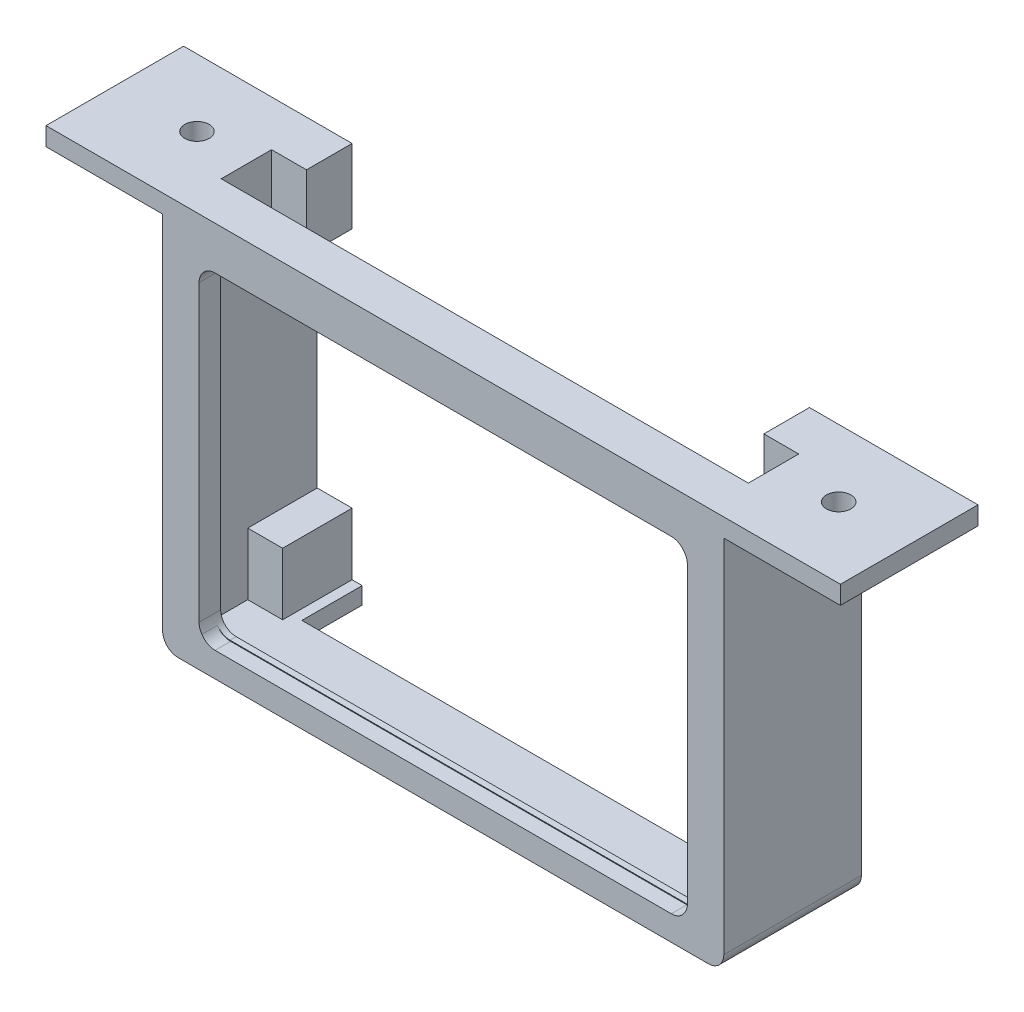
SolidWorks part; units mm, degrees
ref_plane "Front Plane" through (0, 0, 0) normal (0, 0, 1) x (1, 0, 0)
ref_plane "Top Plane" through (0, 0, 0) normal (0, 1, 0) x (1, 0, 0)
ref_plane "Right Plane" through (0, 0, 0) normal (1, 0, 0) x (0, 0, -1)
sketch "Sketch1" plane through (0, 0, 0) normal (0, 0, 1) x (1, 0, 0)
  line L1 (-45.9685, -30.8317) -> (45.9685, -30.8317)
  line L2 (-45.9685, -30.8317) -> (-45.9685, 30.8317)
  line L3 (-45.9685, 30.8317) -> (45.9685, 30.8317)
  line L4 (45.9685, -30.8317) -> (45.9685, 30.8317)
  line L5 (-45.9685, -30.8317) -> (45.9685, 30.8317) construction
  line L6 (-45.9685, 30.8317) -> (45.9685, -30.8317) construction
  line L7 (-43.18, -28.067) -> (43.18, -28.067)
  line L8 (-43.18, -28.067) -> (-43.18, 28.067)
  line L9 (-43.18, 28.067) -> (43.18, 28.067)
  line L10 (43.18, -28.067) -> (43.18, 28.067)
  line L11 (-43.18, -28.067) -> (43.18, 28.067) construction
  line L12 (-43.18, 28.067) -> (43.18, -28.067) construction
  point P0 (0, 0)
  point P6 (0, 0)
extrude "Boss-Extrude1" add sketch "Sketch1" along normal blind 20
sketch "Sketch2" plane through (0, 0, 20) normal (0, 0, 1) x (1, 0, 0)
  line L1 (-43.18, 28.067) -> (43.18, 28.067)
  line L2 (-43.18, 28.067) -> (-43.18, -28.067)
  line L3 (-43.18, -28.067) -> (43.18, -28.067)
  line L4 (43.18, 28.067) -> (43.18, -28.067)
  line L9 (8.8108, -10.2768) -> (-8.8108, 10.2768) construction
  line L10 (8.8108, 10.2768) -> (-8.8108, -10.2768) construction
  line L15 (8.8108, -10.2768) -> (-8.8108, 10.2768) construction
  line L16 (8.8108, 10.2768) -> (-8.8108, -10.2768) construction
  point P6 (0, 0)
  point P12 (0, 0)
extrude "Boss-Extrude3" add sketch "Sketch2" against normal blind 1 contours L2 L1 L4 L3
sketch "Sketch4" plane through (0, 0, 20) normal (0, 0, 1) x (1, 0, 0)
  line L1 (40, -26.64) -> (-40, -26.64)
  line L2 (40, -26.64) -> (40, 26.64)
  line L3 (40, 26.64) -> (-40, 26.64)
  line L4 (-40, -26.64) -> (-40, 26.64)
  line L5 (40, -26.64) -> (-40, 26.64) construction
  line L6 (40, 26.64) -> (-40, -26.64) construction
  point P0 (0, 0)
extrude "Cut-Extrude6" cut sketch "Sketch4" against normal through all
sketch "Sketch5" plane through (0, 30.8317, 0) normal (0, 1, 0) x (1, 0, 0)
  line L0 (45.9685, -20) -> (-45.9685, -20) construction
  line L1 (-77.9537, -20) -> (77.9934, -20)
  line L2 (-77.9537, -20) -> (-77.9537, 0)
  line L3 (-77.9537, 0) -> (77.9934, 0)
  line L4 (77.9934, -20) -> (77.9934, 0)
  line L5 (-77.9537, -20) -> (77.9934, 0) construction
  line L6 (-77.9537, 0) -> (77.9934, -20) construction
  line L7 (45.9685, 0) -> (-45.9685, 0) construction
  point P0 (0.0198, -10)
extrude "Boss-Extrude4" add sketch "Sketch5" along normal blind 3
sketch "Sketch8" plane through (0, 0, 20) normal (0, 0, 1) x (1, 0, 0)
  line L0 (-77.9537, 33.8317) -> (77.9934, 33.8317) construction
  line L1 (45.9685, 30.8317) -> (65.0755, 30.8317)
  line L2 (45.9685, 30.8317) -> (45.9685, 33.8317)
  line L3 (45.9685, 33.8317) -> (65.0755, 33.8317)
  line L4 (65.0755, 30.8317) -> (65.0755, 33.8317)
  line L6 (65.0755, 30.8317) -> (77.9934, 30.8317)
  line L7 (65.0755, 30.8317) -> (65.0755, 33.8317)
  line L8 (65.0755, 33.8317) -> (77.9934, 33.8317)
  line L9 (77.9934, 30.8317) -> (77.9934, 33.8317)
  line M10 (45.9685, 30.8317) -> (77.9934, 30.8317)
  line M11 (77.9934, 30.8317) -> (77.9934, 33.8317)
  line M12 (77.9934, 33.8317) -> (-77.9537, 33.8317)
extrude "Cut-Extrude7" cut sketch "Sketch8" against normal through all contours L4 M10 M11 M12 region at (71.5344, 32.3317, 20)
sketch "Sketch9" plane through (0, 0, 20) normal (0, 0, 1) x (1, 0, 0)
  line L0 (-77.9537, 33.8317) -> (65.0755, 33.8317) construction
  line L1 (-45.9685, 30.8317) -> (-65.0755, 30.8317)
  line L2 (-45.9685, 30.8317) -> (-45.9685, 33.8317)
  line L3 (-45.9685, 33.8317) -> (-65.0755, 33.8317)
  line L4 (-65.0755, 30.8317) -> (-65.0755, 33.8317)
  line L6 (-65.0755, 30.8317) -> (-77.9537, 30.8317)
  line L7 (-65.0755, 30.8317) -> (-65.0755, 33.8317)
  line L8 (-65.0755, 33.8317) -> (-77.9537, 33.8317)
  line L9 (-77.9537, 30.8317) -> (-77.9537, 33.8317)
extrude "Cut-Extrude8" cut sketch "Sketch9" against normal through all contours L7 L6 L9 L8
sketch "Sketch10" plane through (0, 33.8317, 0) normal (0, 1, 0) x (1, 0, 0)
  line L5 (-43.18, -19) -> (43.18, -19) construction
  circle A3 centre (53.2491, -11) radius 2
  circle A4 centre (-51.8815, -11) radius 2
  dimension "D1" = 8
  dimension "D2" = 8
extrude "Cut-Extrude9" cut sketch "Sketch10" against normal through all contours A3
extrude "Cut-Extrude10" cut sketch "Sketch10<3>" against normal through all
sketch "Sketch10<3>" plane through (0, 33.8317, 0) normal (0, 1, 0) x (1, 0, 0) same geometry as "Sketch10"
sketch "Sketch11" plane through (0, 33.8317, 0) normal (0, 1, 0) x (1, 0, 0)
  line L0 (65.0755, 0) -> (-65.0755, 0) construction
  line L1 (37.4668, -15.7312) -> (-37.4668, -15.7312)
  line L2 (37.4668, -15.7312) -> (37.4668, 0)
  line L3 (37.4668, 0) -> (-37.4668, 0)
  line L4 (-37.4668, -15.7312) -> (-37.4668, 0)
  line L5 (37.4668, -15.7312) -> (-37.4668, 0) construction
  line L6 (37.4668, 0) -> (-37.4668, -15.7312) construction
  point P0 (0, -7.8656)
extrude "Cut-Extrude11" cut sketch "Sketch11" against normal blind 20
sketch "Sketch12" plane through (0, 30.8317, 0) normal (0, -1, 0) x (1, 0, 0)
  line L0 (65.0755, 10) -> (53.2491, 11)
  line L1 (65.0755, 0) -> (65.0755, 20) construction
fillet "Fillet1" radius 2.54 1 edges at (40, 26.64, 19.5)
fillet "Fillet2" radius 2.54 1 edges at (-40, 26.64, 19.5)
fillet "Fillet3" radius 2.54 1 edges at (-40, -26.64, 19.5)
fillet "Fillet4" radius 2.54 1 edges at (40, -26.64, 19.5)
fillet "Fillet5" radius 2.54 1 edges at (-45.9685, -30.8317, 10)
fillet "Fillet6" radius 2.54 1 edges at (45.9685, -30.8317, 10)
sketch "Sketch14" plane through (0, 28.067, 0) normal (0, -1, 0) x (1, 0, 0)
  line L0 (37.4668, 15.7312) -> (43.18, 15.7312)
  line L1 (43.18, 19) -> (43.18, 0) construction
  line L4 (37.4668, 0) -> (37.4668, 15.7312) construction
  line L5 (43.18, 15.7312) -> (37.4668, 15.7312)
  line L6 (43.18, 15.7312) -> (43.18, 7.4762)
  line L7 (43.18, 7.4762) -> (37.4668, 7.4762)
  line L8 (37.4668, 15.7312) -> (37.4668, 7.4762)
extrude "Cut-Extrude12" cut sketch "Sketch14" against normal through all contours L6 L5 L8 L7
sketch "Sketch15" plane through (0, 28.067, 0) normal (0, -1, 0) x (1, 0, 0)
  line L0 (-43.18, 19) -> (-43.18, 0) construction
  line L1 (-43.18, 15.7312) -> (-37.4668, 15.7312)
  line L2 (-43.18, 15.7312) -> (-43.18, 7.4762)
  line L3 (-43.18, 7.4762) -> (-37.4668, 7.4762)
  line L4 (-37.4668, 15.7312) -> (-37.4668, 7.4762)
  line L5 (-37.4668, 15.7312) -> (-37.4668, 0) construction
  line L7 (43.18, 15.7312) -> (-37.4668, 15.7312) construction
extrude "Cut-Extrude13" cut sketch "Sketch15" against normal through all
sketch "Sketch16" plane through (43.18, 0, 0) normal (-1, 0, 0) x (0, 0, 1)
  line L0 (7.4762, 33.8317) -> (7.4762, 28.067) construction
  line L1 (0, 28.067) -> (7.4762, 28.067)
  line L2 (0, 28.067) -> (0, 21.717)
  line L3 (0, 21.717) -> (7.4762, 21.717)
  line L4 (7.4762, 28.067) -> (7.4762, 21.717)
extrude "Boss-Extrude5" add sketch "Sketch16" along normal up to surface (5.7132 mm away) up to face at (37.4668, 30.9494, 3.7381)
sketch "Sketch17" plane through (-43.18, 0, 0) normal (1, 0, 0) x (0, 0, -1)
  line L0 (0, 28.067) -> (0, -28.067) construction
  line L1 (-7.4762, 28.067) -> (0, 28.067)
  line L2 (-7.4762, 28.067) -> (-7.4762, 21.717)
  line L3 (-7.4762, 21.717) -> (0, 21.717)
  line L4 (0, 28.067) -> (0, 21.717)
extrude "Boss-Extrude6" add sketch "Sketch17" along normal up to surface (5.7132 mm away) up to face at (-37.4668, 30.9494, 3.7381)
sketch "Sketch18" plane through (-43.18, 0, 0) normal (1, 0, 0) x (0, 0, -1)
  line L0 (-19, -28.067) -> (0, -28.067) construction
  line L1 (-11.38, -28.067) -> (0, -28.067)
  line L2 (-11.38, -28.067) -> (-11.38, -17.907)
  line L3 (-11.38, -17.907) -> (0, -17.907)
  line L4 (0, -28.067) -> (0, -17.907)
  line L5 (0, 21.717) -> (0, -28.067) construction
  dimension "D1" = 7.62
extrude "Boss-Extrude7" add sketch "Sketch18" along normal up to surface (5.7132 mm away) contours L2 L1 L4 L3 up to face at (-37.4668, 27.7744, 3.7381)
sketch "Sketch19" plane through (43.18, 0, 0) normal (-1, 0, 0) x (0, 0, 1)
  line L0 (19, -28.067) -> (0, -28.067) construction
  line L1 (11.38, -28.067) -> (0, -28.067)
  line L2 (11.38, -28.067) -> (11.38, -17.907)
  line L3 (11.38, -17.907) -> (0, -17.907)
  line L4 (0, -28.067) -> (0, -17.907)
  line L5 (19, 28.067) -> (19, -28.067) construction
  line L6 (0, -28.067) -> (0, 21.717) construction
  dimension "D1" = 7.62
  dimension "D2" = 10.16
extrude "Boss-Extrude8" add sketch "Sketch19" along normal up to surface (5.7132 mm away) up to face at (37.4668, 27.7744, 3.7381)
sketch "Sketch20" plane through (0, -30.8317, 0) normal (0, -1, 0) x (1, 0, 0)
  line L0 (-43.4285, 0) -> (43.4285, 0) construction
  line L1 (-35.8085, 9.8863) -> (35.8085, 9.8863)
  line L2 (-35.8085, 9.8863) -> (-35.8085, 0)
  line L3 (-35.8085, 0) -> (35.8085, 0)
  line L4 (35.8085, 9.8863) -> (35.8085, 0)
  line L5 (-35.8085, 9.8863) -> (35.8085, 0) construction
  line L6 (-35.8085, 0) -> (35.8085, 9.8863) construction
  line L7 (-43.4285, 20) -> (-43.4285, 0) construction
  line L8 (43.4285, 0) -> (43.4285, 20) construction
  point P0 (0, 4.9432)
  point P9 (-35.8085, 4.9432)
  dimension "D1" = 7.62
  dimension "D2" = 7.62
extrude "Cut-Extrude14" cut sketch "Sketch20" against normal through all
sketch "Sketch23" plane through (0, 0, 20) normal (0, 0, 1) x (1, 0, 0)
  line L5 (45.9685, -30.8317) -> (-45.9685, 30.8317) construction
  line L6 (45.9685, 30.8317) -> (-45.9685, -30.8317) construction
  line L7 (37.3739, -26.7708) -> (-37.3739, -26.7708)
  line L8 (39.9139, -24.2308) -> (39.9139, 24.2308)
  line L9 (37.3739, 26.7708) -> (-37.3739, 26.7708)
  line L10 (-39.9139, -24.2308) -> (-39.9139, 24.2308)
  line L11 (39.9139, -26.7708) -> (-39.9139, 26.7708) construction
  line L12 (39.9139, 26.7708) -> (-39.9139, -26.7708) construction
  line L13 (43.4285, -30.8317) -> (-43.4285, -30.8317)
  line L14 (45.9685, -28.2917) -> (45.9685, 30.8317)
  line L15 (45.9685, 30.8317) -> (-45.9685, 30.8317)
  line L16 (-45.9685, -28.2917) -> (-45.9685, 30.8317)
  line L17 (45.9685, -30.8317) -> (-45.9685, 30.8317) construction
  line L18 (45.9685, 30.8317) -> (-45.9685, -30.8317) construction
  line L19 (65.0755, 30.8317) -> (-65.0755, 30.8317)
  line L20 (65.0755, 30.8317) -> (65.0755, 33.8317)
  line L21 (65.0755, 33.8317) -> (-65.0755, 33.8317)
  line L22 (-65.0755, 30.8317) -> (-65.0755, 33.8317)
  arc A0 (37.3739, -26.7708) -> (39.9139, -24.2308) centre (37.3739, -24.2308) ccw
  arc A1 (39.9139, 24.2308) -> (37.3739, 26.7708) centre (37.3739, 24.2308) ccw
  arc A2 (-37.3739, 26.7708) -> (-39.9139, 24.2308) centre (-37.3739, 24.2308) ccw
  arc A3 (-37.3739, -26.7708) -> (-39.9139, -24.2308) centre (-37.3739, -24.2308) cw
  arc A8 (-43.4285, -30.8317) -> (-45.9685, -28.2917) centre (-43.4285, -28.2917) cw
  arc A9 (43.4285, -30.8317) -> (45.9685, -28.2917) centre (43.4285, -28.2917) ccw
  point P0 (0, 0)
  point P7 (0, 0)
  point P24 (0, 0)
  line M9 (-43.4285, -30.8317) -> (43.4285, -30.8317)
  arc M10 (43.4285, -30.8317) -> (45.9685, -28.2917) centre (43.4285, -28.2917) ccw
  line M11 (45.9685, -28.2917) -> (45.9685, 30.8317)
  line M17 (-45.9685, 30.8317) -> (-45.9685, -28.2917)
  arc M18 (-45.9685, -28.2917) -> (-43.4285, -30.8317) centre (-43.4285, -28.2917) ccw
  arc M36 (-37.46, -26.64) -> (-40, -24.1) centre (-37.46, -24.1) cw
  line M37 (-40, -24.1) -> (-40, 24.1)
  arc M38 (-40, 24.1) -> (-37.46, 26.64) centre (-37.46, 24.1) cw
  arc M40 (37.46, 26.64) -> (40, 24.1) centre (37.46, 24.1) cw
  line M41 (40, 24.1) -> (40, -24.1)
  arc M42 (40, -24.1) -> (37.46, -26.64) centre (37.46, -24.1) cw
  dimension "D1" = 2.54
  dimension "D2" = 2.54
extrude "Boss-Extrude14" add sketch "Sketch23" along normal blind 2.54 contours L15 L7 A3 A2 L9 A1 A0 M11 M17 M18 M9 M10 M36 M37 M38 M40 M41 M42 | L21 L22 L19 L20 region at (0, -29.7247, 20)
